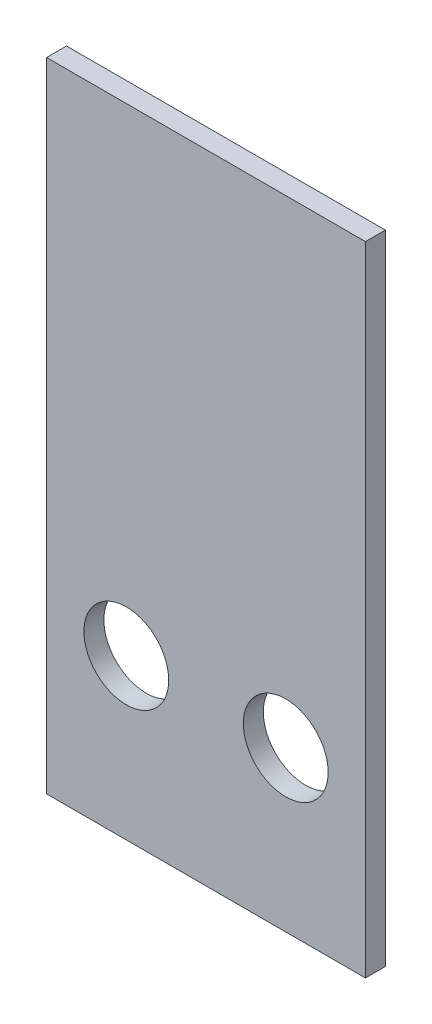
SolidWorks part; units mm, degrees
material "Alumina"
ref_plane "Front Plane" through (0, 0, 0) normal (0, 0, 1) x (1, 0, 0)
ref_plane "Top Plane" through (0, 0, 0) normal (0, 1, 0) x (1, 0, 0)
ref_plane "Right Plane" through (0, 0, 0) normal (1, 0, 0) x (0, 0, -1)
sketch "Sketch1" plane through (0, 0, 0) normal (0, 0, 1) x (1, 0, 0)
  line L1 (-12.7, 25.4) -> (12.7, 25.4)
  line L2 (-12.7, 25.4) -> (-12.7, -25.4)
  line L3 (-12.7, -25.4) -> (12.7, -25.4)
  line L4 (12.7, 25.4) -> (12.7, -25.4)
  line L5 (-12.7, 25.4) -> (12.7, -25.4) construction
  line L6 (-12.7, -25.4) -> (12.7, 25.4) construction
  point P0 (0, 0)
  dimension "D1" = 50.8
  dimension "D2" = 25.4
extrude "Boss-Extrude1" add sketch "Sketch1" along normal blind 1.5875
sketch "Sketch2" plane through (0, 0, 1.5875) normal (0, 0, 1) x (1, 0, 0)
  line L0 (-12.7, -25.4) -> (12.7, -25.4) construction
  line L1 (-12.7, 25.4) -> (-12.7, -25.4) construction
  point P0 (-6.35, -12.7)
  point P1 (6.35, -12.7)
  dimension "D1" = 12.7
  dimension "D2" = 12.7
  dimension "D3" = 6.35
hole_wizard "1/4 Clearance Hole1" positions "Sketch3" profile "Sketch4" hole size "1/4" standard "ANSI Inch" end condition through all
sketch "Sketch3" plane through (0, 0, 1.5875) normal (0, 0, 1) x (1, 0, 0)
  point P0 (-6.35, -12.7)
  point P3 (6.35, -12.7)
sketch "Sketch4" plane through (-6.35, -12.7, 1.5875) normal (1, 0, 0) x (0, -1, 0)
  line L0 (0, 0) -> (0, 1.5875)
  line L1 (0, 1.5875) -> (3.3782, 1.5875)
  line L2 (3.3782, 1.5875) -> (3.3782, 0)
  line L5 (3.3782, 0) -> (0, 0)
  line L11 (0, -6.35) -> (0, 107.95) construction
  dimension "Thru Hole Dia." = 6.7564
  dimension "Thru Hole Depth" = 1.5875
